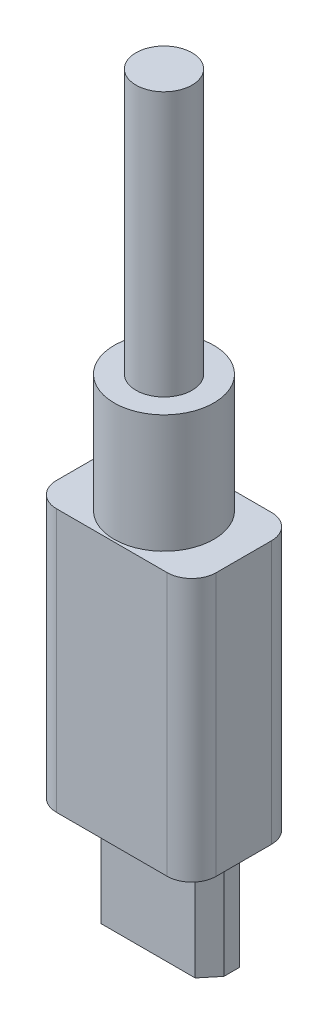
SolidWorks part; units mm, degrees
ref_plane "Front Plane" through (0, 0, 0) normal (0, 0, 1) x (1, 0, 0)
ref_plane "Top Plane" through (0, 0, 0) normal (0, 1, 0) x (1, 0, 0)
ref_plane "Right Plane" through (0, 0, 0) normal (1, 0, 0) x (0, 0, -1)
sketch "Sketch1" plane through (0, 0, 0) normal (0, 1, 0) x (1, 0, 0)
  line L0 (-3.42, 0) -> (-2.68, -0.9)
  line L1 (-2.68, -0.9) -> (2.68, -0.9)
  line L2 (-3.42, 0) -> (-3.42, 0.9)
  line L3 (-3.42, 0.9) -> (3.42, 0.9)
  line L4 (3.42, 0) -> (3.42, 0.9)
  line L5 (-3.42, -0.9) -> (3.42, 0.9) construction
  line L6 (-3.42, 0.9) -> (3.42, -0.9) construction
  line L7 (2.68, -0.9) -> (3.42, 0)
  line L8 (0, 0) -> (0, -0.9) construction
  point P0 (0, 0)
  dimension "D1" = 6.84
  dimension "D2" = 1.8
  dimension "D3" = 5.36
  dimension "D4" = 0.9
extrude "Boss-Extrude1" add sketch "Sketch1" along normal blind 6.3
sketch "Sketch2" plane through (0, 6.3, 0) normal (0, 1, 0) x (1, 0, 0)
  line L1 (-4.555, -2.975) -> (4.555, -2.975)
  line L2 (-4.555, -2.975) -> (-4.555, 2.975)
  line L3 (-4.555, 2.975) -> (4.555, 2.975)
  line L4 (4.555, -2.975) -> (4.555, 2.975)
  line L5 (-4.555, -2.975) -> (4.555, 2.975) construction
  line L6 (-4.555, 2.975) -> (4.555, -2.975) construction
  point P0 (0, 0)
  dimension "D1" = 5.95
  dimension "D2" = 9.11
extrude "Boss-Extrude2" add sketch "Sketch2" along normal blind 15
fillet "Fillet1" radius 1.4 4 edges at (4.555, 13.8, -2.975) (-4.555, 13.8, -2.975) (-4.555, 13.8, 2.975) (4.555, 13.8, 2.975)
sketch "Sketch4" plane through (0, 21.3, 0) normal (0, 1, 0) x (1, 0, 0)
  circle A0 centre (0, 0) radius 2.845
  dimension "D1" = 5.69
extrude "Boss-Extrude3" add sketch "Sketch4" along normal blind 6.74
sketch "Sketch5" plane through (0, 28.04, 0) normal (0, 1, 0) x (1, 0, 0)
  circle A0 centre (0, 0) radius 1.6
  dimension "D1" = 3.2
extrude "Boss-Extrude4" add sketch "Sketch5" along normal blind 15.078
